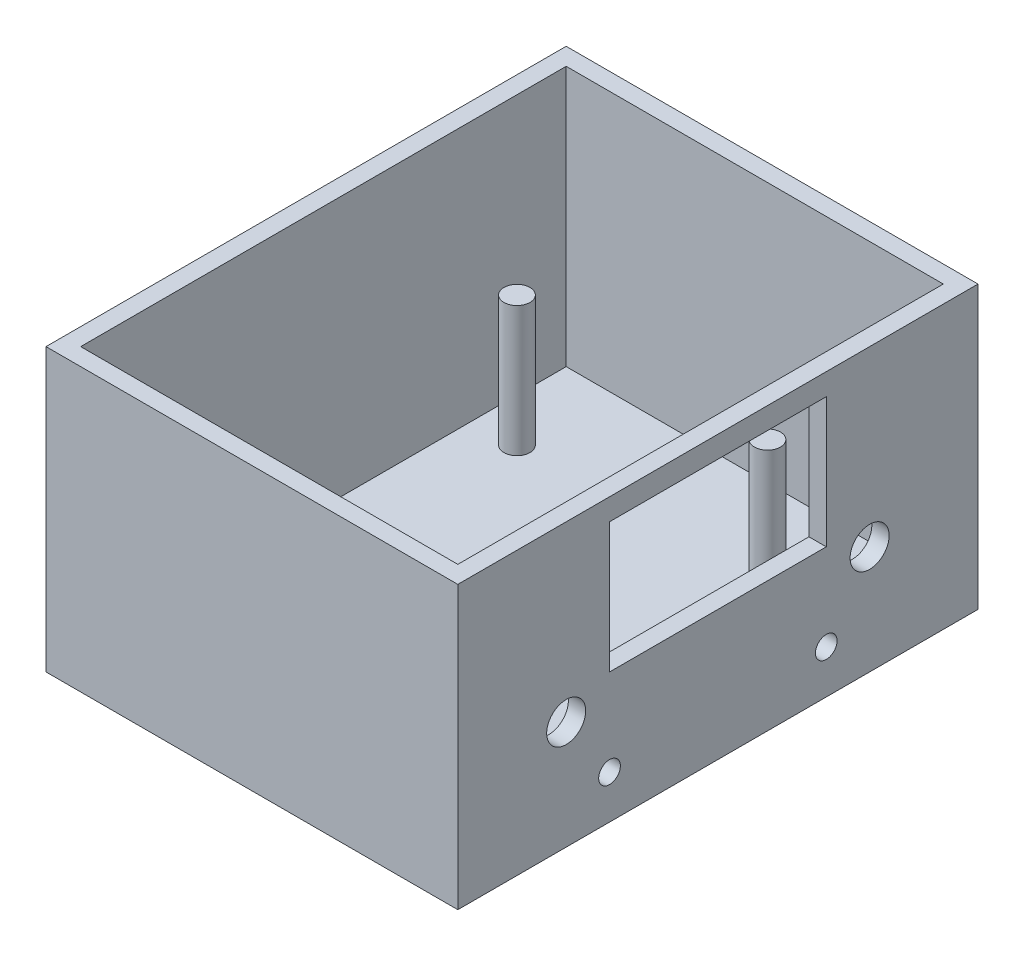
SolidWorks part; units mm, degrees
ref_plane "Front Plane" through (0, 0, 0) normal (0, 0, 1) x (1, 0, 0)
ref_plane "Top Plane" through (0, 0, 0) normal (0, 1, 0) x (1, 0, 0)
ref_plane "Right Plane" through (0, 0, 0) normal (1, 0, 0) x (0, 0, -1)
sketch "Sketch1" plane through (0, 0, 0) normal (0, 1, 0) x (1, 0, 0)
  line L1 (-47.5, -60) -> (47.5, -60)
  line L2 (-47.5, -60) -> (-47.5, 60)
  line L3 (-47.5, 60) -> (47.5, 60)
  line L4 (47.5, -60) -> (47.5, 60)
  line L5 (-47.5, -60) -> (47.5, 60) construction
  line L6 (-47.5, 60) -> (47.5, -60) construction
  point P0 (0, 0)
  dimension "D1" = 120
  dimension "D2" = 95
extrude "base dimensions" add sketch "Sketch1" along normal blind 5
sketch "Sketch2" plane through (0, 5, 0) normal (0, 1, 0) x (1, 0, 0)
  line L0 (47.5, -60) -> (47.5, 60) construction
  line L1 (-47.5, -60) -> (47.5, -60) construction
  line L2 (-47.5, 60) -> (-47.5, -60) construction
  line L3 (47.5, 60) -> (-47.5, 60) construction
  line L4 (47.5, -60) -> (47.5, 60)
  line L5 (-47.5, -60) -> (47.5, -60)
  line L6 (-47.5, 60) -> (-47.5, -60)
  line L7 (47.5, 60) -> (-47.5, 60)
  line L9 (-43.5, -56) -> (43.5, -56)
  line L10 (-43.5, -56) -> (-43.5, 56)
  line L11 (-43.5, 56) -> (43.5, 56)
  line L12 (43.5, -56) -> (43.5, 56)
  line L13 (-43.5, -56) -> (43.5, 56) construction
  line L14 (-43.5, 56) -> (43.5, -56) construction
  point P4 (0, 0)
  dimension "D1" = 4
  dimension "D2" = 4
extrude "wall height and depth" add sketch "Sketch2" along normal blind 60
sketch "Sketch3" plane through (0, 5, 0) normal (0, 1, 0) x (1, 0, 0)
  line L0 (-43.5, 56) -> (-43.5, -56) construction
  line L1 (-43.5, -56) -> (43.5, -56) construction
  circle A0 centre (-33.5, 34.645) radius 3
  circle A1 centre (-33.5, -46) radius 3
  circle A2 centre (37.62, -46) radius 3
  circle A3 centre (24.285, 34.645) radius 3
  point P8 (12.1665, 23.4734)
  point P9 (-33.59, -22.2832)
  dimension "D4" = 6
  dimension "D1" = 57.785
  dimension "D2" = 71.12
  dimension "D3" = 80.645
  dimension "D5" = 10
  dimension "D6" = 10
extrude "support pegs" add sketch "Sketch3" along normal blind 30
sketch "Sketch4" plane through (47.5, 0, 0) normal (1, 0, 0) x (0, 0, -1)
  line L0 (0, 71.0913) -> (0, -6.0913) construction
  line L1 (-25, 60) -> (25, 60)
  line L2 (-25, 60) -> (-25, 30)
  line L3 (-25, 30) -> (25, 30)
  line L4 (25, 60) -> (25, 30)
  line L5 (-25, 60) -> (25, 30) construction
  line L6 (-25, 30) -> (25, 60) construction
  line L7 (52.25, 0) -> (-52.25, 0) construction
  line L8 (-60, 65) -> (60, 65) construction
  circle A0 centre (-35, 25) radius 4.5
  circle A1 centre (-25, 10) radius 2.5
  circle A2 centre (25, 10) radius 2.5
  circle A3 centre (35, 25) radius 4.5
  point P0 (0, 45)
  point P12 (25, 10)
  dimension "D3" = 9
  dimension "D4" = 5
  dimension "D1" = 25
  dimension "D2" = 35
  dimension "D5" = 10
  dimension "D6" = 25
  dimension "D7" = 30
  dimension "D8" = 50
  dimension "D9" = 20
extrude "front holes" cut sketch "Sketch4" against normal up to surface (4 mm away) up to face at (43.5, 35, 0)
